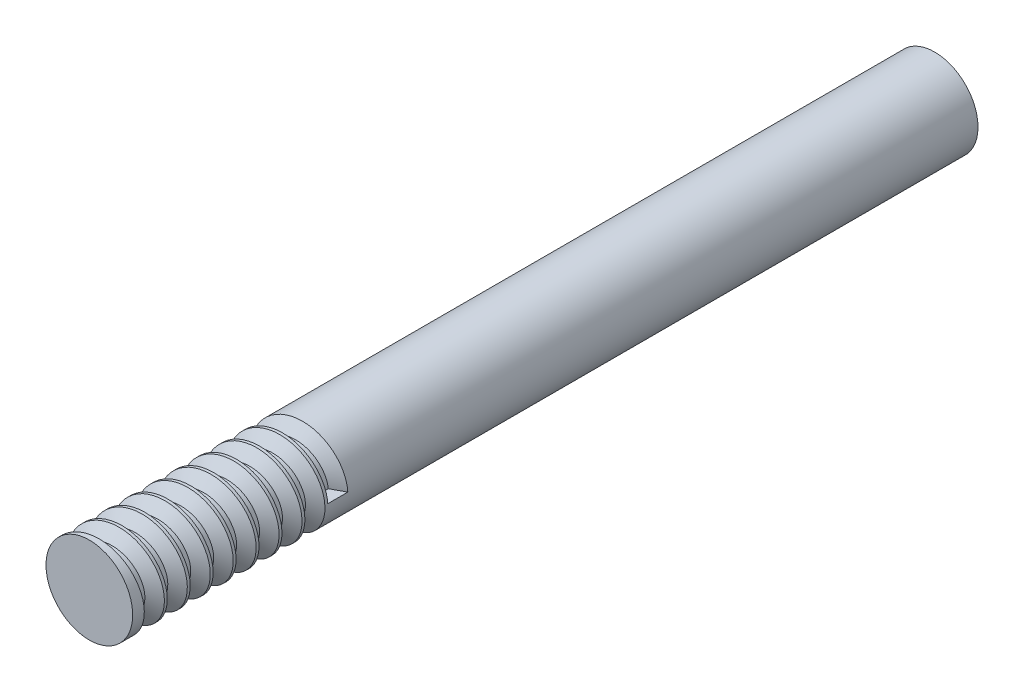
SolidWorks part; units mm, degrees
ref_plane "前视基准面" through (0, 0, 0) normal (0, 0, 1) x (1, 0, 0)
ref_plane "上视基准面" through (0, 0, 0) normal (0, 1, 0) x (1, 0, 0)
ref_plane "右视基准面" through (0, 0, 0) normal (1, 0, 0) x (0, 0, -1)
other "Configuration Table"
sketch "草图1" plane through (0, 0, 0) normal (0, 0, 1) x (1, 0, 0)
  circle A0 centre (0, 0) radius 4
  dimension "D1" = 8
extrude "凸台-拉伸1" add sketch "草图1" along normal blind 60
extrude "凸台-拉伸2" add sketch "草图1<2>" along normal blind 18 from surface starting at face at (4, 0, 60)
sketch "草图1<2>" plane through (0, 0, 0) normal (0, 0, 1) x (1, 0, 0) same geometry as "草图1"
thread "螺纹线1" pitch 2.1167 method cut profile "螺纹线轮廓1" start angle 0, offset 0, length 18, pitch 2.1167, diameter 8
ref_plane "基准面1" through (-4, 0, 78) normal (0, -1, 0) x (-1, 0, 0)
sketch "螺纹线轮廓1" plane through (-4, 0, 78) normal (0, -1, 0) x (-1, 0, 0)
  line L0 (0, 0) -> (0, 2.1167) construction
  line L11 (0, 0) -> (0, 1.8521)
  line L12 (0, 1.8521) -> (-1.1457, 1.1906)
  line L13 (-1.1457, 1.1906) -> (-1.1457, 0.6615)
  line L15 (-1.1457, 0.6615) -> (0, 0)
  line L17 (-1.1457, 0.926) -> (0, 0.926) construction
  point P2 (0, 0)
  dimension "Pitch" = 2.1167
  dimension "Profile_Angle" = 60
  dimension "Profile_Land" = 0.5292
  dimension "Profile_Height" = 1.1457
